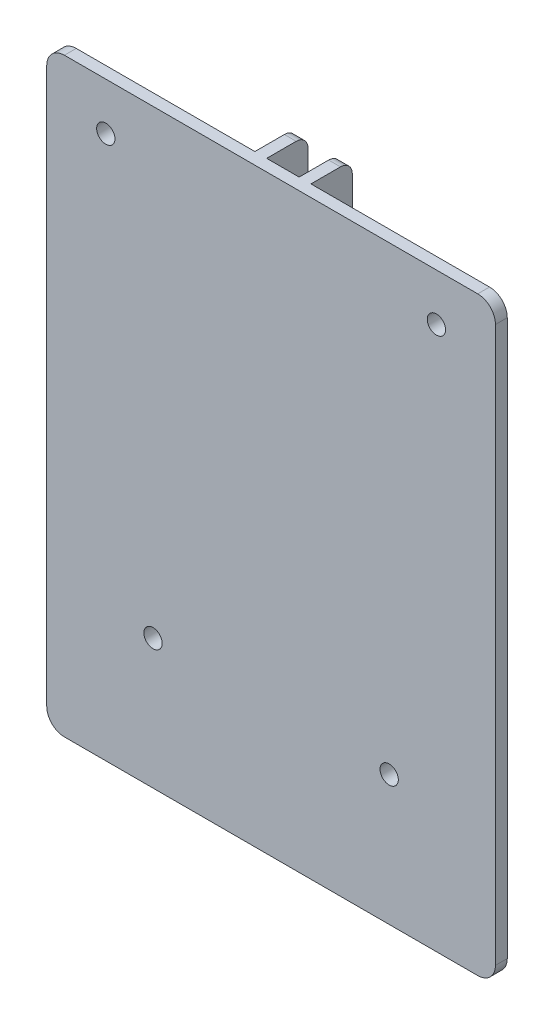
SolidWorks part; units mm, degrees
ref_plane "Plan de face" through (0, 0, 0) normal (0, 0, 1) x (1, 0, 0)
ref_plane "Plan de dessus" through (0, 0, 0) normal (0, 1, 0) x (1, 0, 0)
ref_plane "Plan de droite" through (0, 0, 0) normal (1, 0, 0) x (0, 0, -1)
sketch "Esquisse1" plane through (0, 0, 0) normal (0, 0, 1) x (1, 0, 0)
  line L1 (0, 0) -> (76, 0)
  line L2 (0, 0) -> (0, 100)
  line L3 (0, 100) -> (76, 100)
  line L4 (76, 0) -> (76, 100)
extrude "Boss.-Extru.1" add sketch "Esquisse1" along normal blind 9
sketch "Esquisse2" plane through (0, 0, 0) normal (0, 0, -1) x (-1, 0, 0)
  line L1 (-33.25, 100) -> (0, 100)
  line L2 (-33.25, 100) -> (-33.25, 0)
  line L3 (-33.25, 0) -> (0, 0)
  line L4 (0, 100) -> (0, 0)
  line L5 (-76, 100) -> (-42.75, 100)
  line L6 (-76, 100) -> (-76, 0)
  line L7 (-76, 0) -> (-42.75, 0)
  line L8 (-42.75, 100) -> (-42.75, 0)
  line L9 (-35.25, 100) -> (-40.75, 100)
  line L10 (-35.25, 100) -> (-35.25, 0)
  line L11 (-35.25, 0) -> (-40.75, 0)
  line L12 (-40.75, 100) -> (-40.75, 0)
extrude "Enlèv. mat.-Extru.1" cut sketch "Esquisse2" against normal blind 7
sketch "Esquisse3" plane through (42.75, 0, 0) normal (1, 0, 0) x (0, 0, -1)
  circle A0 centre (-3.5, 20) radius 1.55
  circle A1 centre (-3.5, 90) radius 1.55
  point P2 (0, 0)
  point P5 (0, 0)
  point P6 (0, 0)
extrude "Enlèv. mat.-Extru.2" cut sketch "Esquisse3" against normal through all
fillet "Congé1" radius 3 4 edges at (0, 0, 8) (76, 0, 8) (0, 100, 8) (76, 100, 8)
fillet "Congé2" radius 2 4 edges at (34.25, 0, 0) (41.75, 0, 0) (34.25, 100, 0) (41.75, 100, 0)
sketch "Esquisse9" plane through (0, 0, 7) normal (0, 0, -1) x (-1, 0, 0)
  circle A1 centre (-66, 92) radius 3
  circle A2 centre (-10, 92) radius 3
  circle A3 centre (-18, 22) radius 3
  circle A4 centre (-58, 22) radius 3
  point P8 (0, 0)
  point P9 (0, 0)
  point P10 (0, 0)
  point P11 (0, 0)
  point P12 (0, 0)
  point P13 (0, 0)
  point P14 (0, 0)
  point P15 (0, 0)
extrude "Boss.-Extru.2" add sketch "Esquisse9" along normal blind 3
sketch "Esquisse5" plane through (0, 0, 7) normal (0, 0, -1) x (-1, 0, 0)
  circle A0 centre (-66, 92) radius 1.55
  circle A1 centre (-58, 22) radius 1.55
  circle A2 centre (-18, 22) radius 1.55
  circle A3 centre (-10, 92) radius 1.55
  point P8 (0, 0)
  point P9 (0, 0)
  point P10 (0, 0)
  point P11 (0, 0)
  point P12 (0, 0)
  point P13 (0, 0)
  point P14 (0, 0)
  point P15 (0, 0)
extrude "Enlèv. mat.-Extru.4" cut sketch "Esquisse5" against normal through all both and the other way through all
